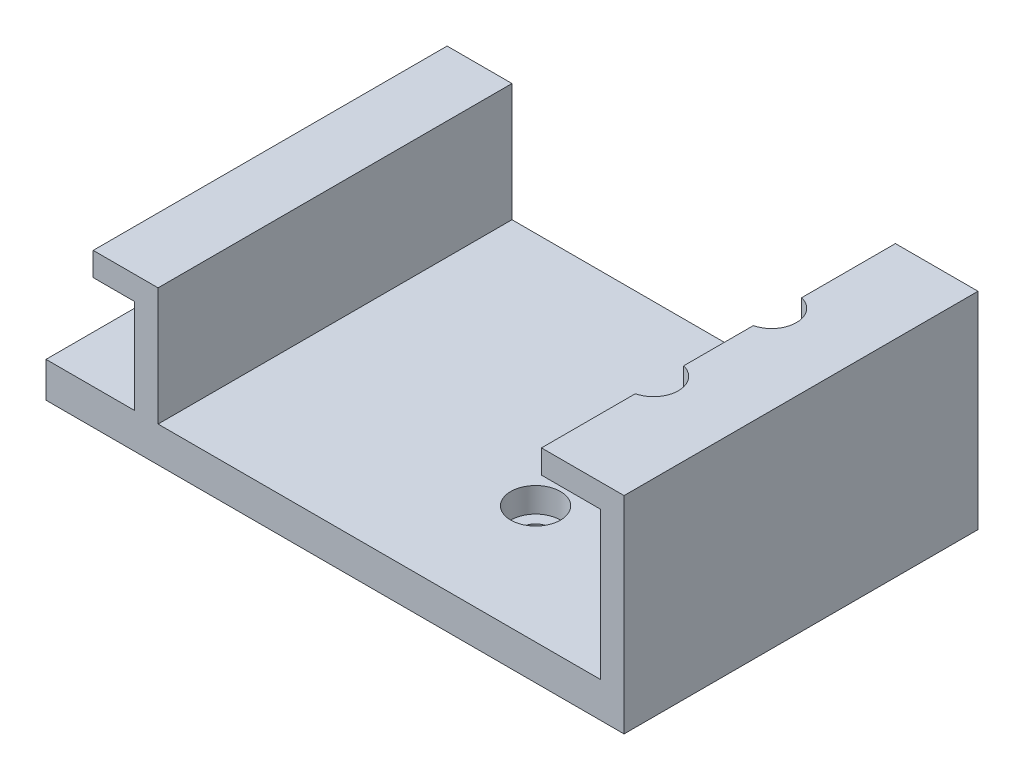
SolidWorks part; units mm, degrees
ref_plane "Front Plane" through (0, 0, 0) normal (0, 0, 1) x (1, 0, 0)
ref_plane "Top Plane" through (0, 0, 0) normal (0, 1, 0) x (1, 0, 0)
ref_plane "Right Plane" through (0, 0, 0) normal (1, 0, 0) x (0, 0, -1)
sketch "Sketch1" plane through (0, 0, 0) normal (0, 0, 1) x (1, 0, 0)
  line L0 (-14, 0) -> (0, 0)
  line L1 (0, 0) -> (0, -35)
  line L2 (0, -35) -> (-98, -35)
  line L3 (-98, -35) -> (-98, -29)
  line L4 (-98, -29) -> (-83, -29)
  line L5 (-83, -29) -> (-83, -13)
  line L6 (-83, -13) -> (-90, -13)
  line L7 (-90, -13) -> (-90, -9)
  line L8 (-90, -9) -> (-79, -9)
  line L9 (-79, -9) -> (-79, -29)
  line L10 (-79, -29) -> (-4, -29)
  line L11 (-4, -29) -> (-4, -4)
  line L12 (-4, -4) -> (-14, -4)
  line L13 (-14, -4) -> (-14, 0)
  dimension "D1" = 25
  dimension "D2" = 75
  dimension "D3" = 6
  dimension "D4" = 6
  dimension "D5" = 4
  dimension "D6" = 4
  dimension "D7" = 4
  dimension "D8" = 4
  dimension "D9" = 10
  dimension "D10" = 16
  dimension "D11" = 7
  dimension "D12" = 15
extrude "Extrude-Base" add sketch "Sketch1" along normal mid plane 60
sketch "Sketch2" plane through (0, -29, 0) normal (0, 1, 0) x (1, 0, 0)
  line L0 (-15, -10) -> (-15, 10) construction
  line L1 (-15, 10) -> (-35, 10) construction
  line L2 (-35, 10) -> (-35, -10) construction
  line L3 (-35, -10) -> (-15, -10) construction
  line L4 (0, -30) -> (0, 30) construction
  line L5 (0, 0) -> (-35, 0) construction
  circle A0 centre (-15, -10) radius 2.2
  circle A1 centre (-15, 10) radius 2.2
  circle A2 centre (-35, 10) radius 2.2
  circle A3 centre (-35, -10) radius 2.2
  point P6 (-15, 0)
  point P9 (0, 0)
  dimension "D4" = 4.4
  dimension "D5" = 4.4
  dimension "D6" = 4.4
  dimension "D7" = 4.4
  dimension "D1" = 15
  dimension "D2" = 20
  dimension "D3" = 20
extrude "Cut-Bolt Holes" cut sketch "Sketch2" against normal blind 10
sketch "Sketch3" plane through (0, -29, 0) normal (0, 1, 0) x (1, 0, 0)
  circle A0 centre (-35, 10) radius 4.215
  circle A1 centre (-15, 10) radius 4.215
  circle A2 centre (-15, -10) radius 4.215
  circle A3 centre (-35, -10) radius 4.215
  circle A4 centre (-35, -10) radius 2.2 construction
  circle A5 centre (-15, -10) radius 2.2 construction
  circle A6 centre (-15, 10) radius 2.2 construction
  circle A7 centre (-35, 10) radius 2.2 construction
  dimension "D1" = 8.43
  dimension "D2" = 8.43
  dimension "D3" = 8.43
  dimension "D4" = 8.43
extrude "Cut-Bolt Head Insets" cut sketch "Sketch3" against normal blind 4.2 and the other way blind 40
sketch "Sketch4" plane through (-98, 0, 0) normal (-1, 0, 0) x (0, 0, 1)
  line L0 (30, -35) -> (-30, -35) construction
  line L1 (20, -35) -> (-20, -35)
  line L2 (20, -35) -> (20, -32)
  line L3 (20, -32) -> (-20, -32)
  line L4 (-20, -35) -> (-20, -32)
  point P7 (0, -35)
  point P8 (0, -35)
  dimension "D1" = 40
  dimension "D2" = 3
extrude "Cut-Top Clearance Slot" cut sketch "Sketch4" against normal blind 45
fillet "Fillet-Clearance Slot Pt 1" radius 3 2 edges at (-75.5, -32, 20) (-75.5, -32, -20)
fillet "Fillet-Clearance Slot Pt 2" radius 3 2 edges at (-75.5, -35, 20) (-75.5, -35, -20)
equation "\"holeBoltDiam\"=4.4"
equation "\"D4@Sketch2\"=\"holeBoltDiam\""
equation "\"D5@Sketch2\"=\"holeBoltDiam\""
equation "\"D6@Sketch2\"=\"holeBoltDiam\""
equation "\"D7@Sketch2\"=\"holeBoltDiam\""
equation "\"insetBoltHead\"=8.43"
equation "\"D1@Sketch3\"=\"insetBoltHead\""
equation "\"D2@Sketch3\"=\"insetBoltHead\""
equation "\"D3@Sketch3\"=\"insetBoltHead\""
equation "\"D4@Sketch3\"=\"insetBoltHead\""
